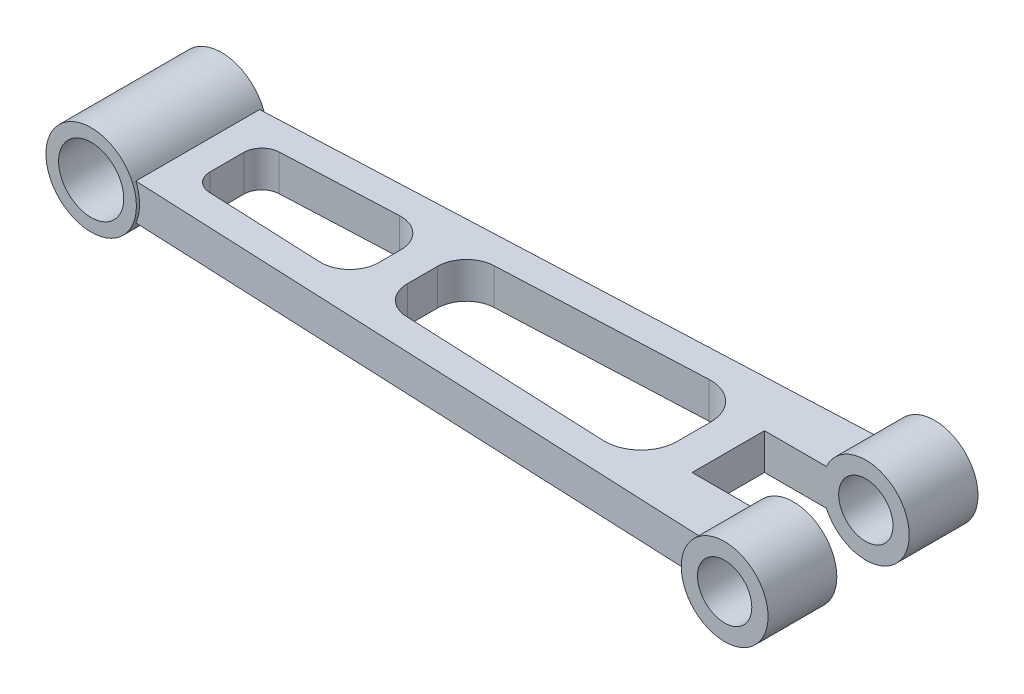
SolidWorks part; units mm, degrees
ref_plane "Front Plane" through (0, 0, 0) normal (0, 0, 1) x (1, 0, 0)
ref_plane "Top Plane" through (0, 0, 0) normal (0, 1, 0) x (1, 0, 0)
ref_plane "Right Plane" through (0, 0, 0) normal (1, 0, 0) x (0, 0, -1)
sketch "Sketch1" plane through (0, 0, 0) normal (0, 1, 0) x (1, 0, 0)
  line L16 (-82.75, 0) -> (-82.75, 17.0543)
  line L17 (-82.75, 17.0543) -> (82.75, 24.2802)
  line L18 (82.75, 24.2802) -> (82.75, 0)
  line L19 (82.75, 0) -> (-82.75, 0)
  point P2 (-55.25, 18.255)
  dimension "D1" = 2.5
  dimension "D2" = 165.5
  dimension "D3" = 82.75
  dimension "D4" = 27.5
  dimension "D5" = 18.255
  dimension "D6" = 24.2802
extrude "Boss-Extrude1" add sketch "Sketch1" along normal blind 10
mirror "Mirror1" about plane through (0, 0, 0) normal (0, 0, 1) of "Boss-Extrude1"
sketch "Sketch2" plane through (0, 10, 0) normal (0, 1, 0) x (1, 0, 0)
  line L0 (-68.9681, 9.6484) -> (-37.099, 11.0399)
  line L1 (-28.75, 3.0475) -> (-28.75, -3.0475)
  line L2 (-37.099, -11.0399) -> (-68.9681, -9.6484)
  line L3 (-73.75, -4.6532) -> (-73.75, 4.6532)
  line L4 (-19.75, 4.139) -> (-19.75, -4.139)
  line L5 (-12.099, -12.1314) -> (44.8138, -14.6163)
  line L6 (55.25, -4.6258) -> (55.25, 4.6258)
  line L7 (44.8138, 14.6163) -> (-12.099, 12.1314)
  line L8 (82.75, -24.2802) -> (82.75, 24.2802) construction
  line L9 (64.75, 10) -> (109.7894, 10)
  line L10 (64.75, 10) -> (64.75, -10)
  line L11 (64.75, -10) -> (109.7894, -10)
  line L12 (109.7894, 10) -> (109.7894, -10)
  line L13 (116.3726, 31.1387) -> (116.3726, -26.8613) construction
  line L14 (82.75, 24.2802) -> (-82.75, 17.0543) construction
  line L15 (82.75, -24.2802) -> (-82.75, -17.0543) construction
  line L16 (-82.75, 17.0543) -> (-82.75, -17.0543) construction
  arc A0 (-68.9681, 9.6484) -> (-73.75, 4.6532) centre (-68.75, 4.6532) ccw
  arc A1 (-68.9681, -9.6484) -> (-73.75, -4.6532) centre (-68.75, -4.6532) cw
  arc A2 (-28.75, -3.0475) -> (-37.099, -11.0399) centre (-36.75, -3.0475) cw
  arc A3 (-37.099, 11.0399) -> (-28.75, 3.0475) centre (-36.75, 3.0475) cw
  arc A4 (-19.75, -4.139) -> (-12.099, -12.1314) centre (-11.75, -4.139) ccw
  arc A5 (-19.75, 4.139) -> (-12.099, 12.1314) centre (-11.75, 4.139) cw
  arc A6 (44.8138, -14.6163) -> (55.25, -4.6258) centre (45.25, -4.6258) ccw
  arc A7 (55.25, 4.6258) -> (44.8138, 14.6163) centre (45.25, 4.6258) ccw
  point P38 (-82.75, 0)
  point P40 (64.75, 0)
  dimension "D10" = 5
  dimension "D11" = 8
  dimension "D12" = 8
  dimension "D13" = 10
  dimension "D1" = 45
  dimension "D2" = 75
  dimension "D3" = 18
  dimension "D4" = 8
  dimension "D5" = 8
  dimension "D6" = 8
  dimension "D7" = 8
  dimension "D8" = 9
  dimension "D9" = 9
  dimension "D14" = 58
  dimension "D15" = 20
extrude "Cut-Extrude1" cut sketch "Sketch2" against normal through all
sketch "Sketch3" plane through (0, 0, 0) normal (0, 0, 1) x (1, 0, 0)
  line L0 (-80.75, 25.5978) -> (-80.75, -9.5055) construction
  line L1 (-82.75, 10) -> (-82.75, 0) construction
  circle A0 centre (-93.25, 5) radius 12.5
  point P7 (0, 0)
  dimension "D2" = 25
  dimension "D1" = 5
  dimension "D3" = 2
extrude "Boss-Extrude2" add sketch "Sketch3" along normal blind 18 and the other way blind 18 separate body
sketch "Sketch4" plane through (0, 0, 18) normal (0, 0, 1) x (1, 0, 0)
  circle A0 centre (-93.25, 5) radius 9
  dimension "D1" = 18
extrude "Cut-Extrude2" cut sketch "Sketch4" against normal through all
sketch "Sketch5" plane through (-0.9006, 0, 20.6279) normal (-0.0436, 0, 0.999) x (0.999, 0, 0.0436)
  line L0 (81.7303, 22.3985) -> (81.7303, -15.8664) construction
  line L1 (83.7303, 10) -> (83.7303, 0) construction
  circle A0 centre (93.7303, 5) radius 12
  dimension "D2" = 24
  dimension "D1" = 5
  dimension "D3" = 2
sketch "Sketch7" plane through (0, 0, 0) normal (0, 0, 1) x (1, 0, 0)
  line L0 (80.7519, 22.3985) -> (80.7519, -15.8664) construction
  circle A0 centre (92.7405, 5) radius 11.9886
extrude "Boss-Extrude4" add sketch "Sketch7" along normal blind 29 and the other way blind 29
sketch "Sketch8" plane through (0, 0, 29) normal (0, 0, 1) x (1, 0, 0)
  circle A0 centre (92.7405, 5) radius 7.5
  dimension "D1" = 15
extrude "Cut-Extrude3" cut sketch "Sketch8" against normal through all
extrude "Cut-Extrude4" cut sketch "Sketch2<2>" against normal through all
sketch "Sketch2<2>" plane through (0, 10, 0) normal (0, 1, 0) x (1, 0, 0) same geometry as "Sketch2"
extrude "Cut-Extrude5" cut sketch "Sketch2<3>" against normal through all and the other way through all
sketch "Sketch2<3>" plane through (0, 10, 0) normal (0, 1, 0) x (1, 0, 0) same geometry as "Sketch2"
